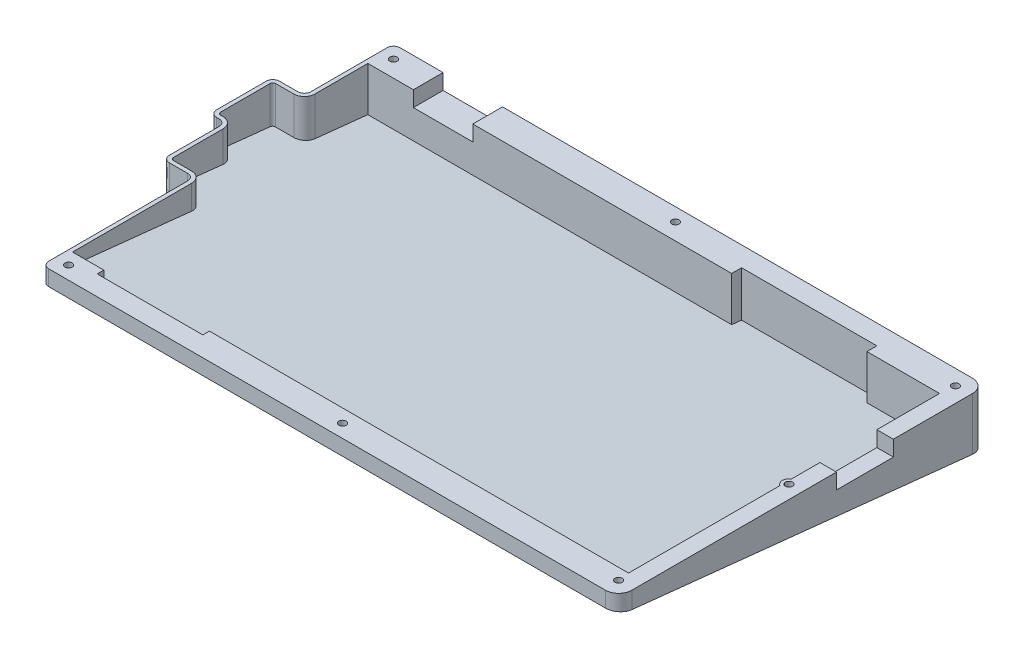
SolidWorks part; units mm, degrees
ref_plane "Front Plane" through (0, 0, 0) normal (0, 0, 1) x (1, 0, 0)
ref_plane "Top Plane" through (0, 0, 0) normal (0, 1, 0) x (1, 0, 0)
ref_plane "Right Plane" through (0, 0, 0) normal (1, 0, 0) x (0, 0, -1)
sketch "Sketch1" plane through (0, 0, 0) normal (0, 1, 0) x (1, 0, 0)
  line L0 (138.4196, 31.7518) -> (125.4196, 31.7518)
  line L1 (-35.0204, 31.7518) -> (107.4196, 31.7518)
  line L2 (140.4196, 29.7518) -> (140.4196, 6.7018)
  line L3 (-34.0204, 3.7518) -> (-34.0204, 22.7518)
  line L4 (136.4596, 27.7518) -> (136.4396, 27.7518)
  line L5 (142.4196, 4.7018) -> (147.9496, 4.7018)
  line L6 (-34.0204, 22.7518) -> (-12.0204, 22.7518)
  line L8 (149.9496, 2.7018) -> (149.9496, -12.3482)
  line L11 (147.9496, -14.3482) -> (147.1896, -14.3482)
  line L14 (145.1896, -16.3482) -> (145.1896, -31.3982)
  line L17 (143.1896, -33.3982) -> (137.6696, -33.3982)
  line L20 (135.6696, -35.3982) -> (135.6696, -77.4982)
  line L21 (-34.0204, -25.6003) -> (-34.0204, -71.4982)
  line L23 (133.6696, -79.4982) -> (-35.0204, -79.4982)
  line L28 (-39.0204, 27.7518) -> (-39.0204, 3.7518)
  line L31 (-34.0204, 3.7518) -> (-39.0204, 3.7518)
  line L32 (-34.0204, -13.4982) -> (-39.0204, -13.4982)
  line L33 (-39.0204, -75.4982) -> (-39.0204, -13.4982)
  line L34 (-34.0204, -71.4982) -> (92.9796, -71.4982)
  line L35 (92.9796, -71.4982) -> (92.9796, -73.4982)
  line L36 (92.9796, -73.4982) -> (124.9796, -73.4982)
  line L37 (124.9796, -73.4982) -> (124.9796, -71.4982)
  line L39 (134.4706, -35.3982) -> (134.4706, -71.4982)
  line L40 (134.4706, -71.4982) -> (124.9796, -71.4982)
  line L41 (137.6696, -32.1992) -> (143.1896, -32.1992)
  line L42 (-34.0204, -13.4982) -> (-34.0204, -22.1362)
  line L43 (143.9906, -31.3982) -> (143.9906, -16.3482)
  line L44 (-12.0204, 22.7518) -> (-12.0204, 25.7518)
  line L45 (147.1896, -13.1492) -> (147.9496, -13.1492)
  line L46 (148.7506, -12.3482) -> (148.7506, 2.7018)
  line L47 (-12.0204, 25.7518) -> (28.9796, 25.7518)
  line L48 (28.9796, 25.7518) -> (28.9796, 22.7518)
  line L49 (28.9796, 22.7518) -> (107.4196, 22.7518)
  line L50 (147.9496, 3.5027) -> (142.4196, 3.5027)
  line L51 (107.4196, 22.7518) -> (107.4196, 31.7518)
  line L52 (139.2206, 6.7018) -> (139.2206, 22.7518)
  line L53 (125.4196, 31.7518) -> (125.4196, 22.7518)
  line L54 (139.2206, 22.7518) -> (125.4196, 22.7518)
  arc A0 (138.4196, 31.7518) -> (140.4196, 29.7518) centre (138.4196, 29.7518) cw
  arc A1 (140.4196, 6.7018) -> (142.4196, 4.7018) centre (142.4196, 6.7018) ccw
  arc A2 (149.9496, 2.7018) -> (147.9496, 4.7018) centre (147.9496, 2.7018) ccw
  arc A3 (149.9496, -12.3482) -> (147.9496, -14.3482) centre (147.9496, -12.3482) cw
  arc A4 (147.1896, -14.3482) -> (145.1896, -16.3482) centre (147.1896, -16.3482) ccw
  arc A5 (145.1896, -31.3982) -> (143.1896, -33.3982) centre (143.1896, -31.3982) cw
  arc A6 (-35.0204, 31.7518) -> (-39.0204, 27.7518) centre (-35.0204, 27.7518) ccw
  arc A7 (-39.0204, -75.4982) -> (-35.0204, -79.4982) centre (-35.0204, -75.4982) ccw
  arc A8 (133.6696, -79.4982) -> (135.6696, -77.4982) centre (133.6696, -77.4982) ccw
  arc A9 (135.6696, -35.3982) -> (137.6696, -33.3982) centre (137.6696, -35.3982) cw
  circle A10 centre (-34.4204, 27.1518) radius 1.1
  circle A11 centre (51.0096, 27.7518) radius 1.1
  circle A12 centre (136.4396, 27.7518) radius 1.1
  circle A13 centre (-34.4204, -74.8982) radius 1.1
  circle A14 centre (48.6296, -75.4982) radius 1.1
  circle A15 centre (131.6496, -75.4982) radius 1.1
  circle A16 centre (-35.0204, -23.8682) radius 1.1
  arc A27 (-34.0204, -22.1362) -> (-34.0204, -25.6003) centre (-35.0204, -23.8682) cw
  arc A28 (139.2206, 6.7018) -> (142.4196, 3.5027) centre (142.4196, 6.7018) ccw
  arc A29 (147.9496, 3.5027) -> (148.7506, 2.7018) centre (147.9496, 2.7018) cw
  arc A30 (148.7506, -12.3482) -> (147.9496, -13.1492) centre (147.9496, -12.3482) cw
  arc A31 (147.1896, -13.1492) -> (143.9906, -16.3482) centre (147.1896, -16.3482) ccw
  arc A32 (143.9906, -31.3982) -> (143.1896, -32.1992) centre (143.1896, -31.3982) cw
  arc A33 (137.6696, -32.1992) -> (134.4706, -35.3982) centre (137.6696, -35.3982) ccw
extrude "Boss-Extrude2" add sketch "Sketch1" against normal blind 4.7 contours L41 A33 L39 L40 L37 L36 L35 L34 L21 A27 L42 L32 L33 A7 L23 A8 L20 A9 L17 A5 L14 A4 L11 A3 L8 A2 L5 A1 L2 A0 L0 L53 L54 L52 A28 L50 A29 L46 A30 L45 A31 L43 A32 A12 A13 A14 A15 | L1 A6 L28 L31 L3 L6 L44 L47 L48 L49 L51 A11 A10 region at (138.2833, 0, -29.6154) region at (31.7683, 0, -26.4895)
move or copy body "Body-Move/Copy1" bodies to move or copy 105 104 copy no rotation origin (55.4646, -2.35, 0) rotation axis (0, 0, 1) rotation angle 180
sketch "Sketch3" plane through (149.9496, 0, 0) normal (1, 0, 0) x (0, 0, -1)
  line L0 (-79.4982, 0) -> (-79.4982, -4.7) construction
  line L1 (-79.4982, 0) -> (-79.4982, -4.7)
  line L2 (31.7518, 0) -> (31.7518, -4.7) construction
  line L3 (31.7518, 0) -> (31.7518, -4.7)
  line L5 (-79.4982, -4.7) -> (31.7518, -16.3928)
  line L6 (31.7518, -16.3928) -> (31.7518, -4.7)
  line L7 (31.7518, -4.7) -> (-79.4982, -4.7)
  line M3 (-75.4982, -4.7) -> (-13.4982, -4.7)
  dimension "D1" = 6
extrude "Boss-Extrude3" add sketch "Sketch3" against normal up to surface (188.97 mm away) contours L6 L7 L5 M3 region at (149.9496, -8.5976, 5.3315) up to face at (-39.0204, -2.35, 4.8232)
sketch "Sketch4" plane through (0, -4.7, 0) normal (0, 1, 0) x (1, 0, 0)
  line L2 (145.9496, -79.4982) -> (149.9496, -79.4982)
  line L3 (149.9496, -79.4982) -> (149.9496, -75.4982)
  line L4 (-29.4904, 6.7018) -> (-29.4904, 29.7518)
  line L5 (-27.4904, 31.7518) -> (-39.0204, 31.7518)
  line L6 (-36.2604, -14.3482) -> (-37.0204, -14.3482)
  line L7 (-39.0204, -12.3482) -> (-39.0204, -79.4982)
  line L8 (-39.0204, -79.4982) -> (-22.7404, -79.4982)
  line L9 (-24.7404, -77.4982) -> (-24.7404, -35.3982)
  line L10 (-26.7404, -33.3982) -> (-32.2604, -33.3982)
  line L11 (-34.2604, -31.3982) -> (-34.2604, -16.3482)
  line L12 (-36.2604, -14.3482) -> (-37.0204, -14.3482)
  line L13 (-39.0204, -12.3482) -> (-39.0204, -79.4982)
  line L14 (-39.0204, -79.4982) -> (-22.7404, -79.4982)
  line L15 (-24.7404, -77.4982) -> (-24.7404, -35.3982)
  line L16 (-26.7404, -33.3982) -> (-32.2604, -33.3982)
  line L17 (-34.2604, -31.3982) -> (-34.2604, -16.3482)
  line L18 (-39.0204, 31.7518) -> (-39.0204, 2.7018)
  line L19 (-37.0204, 4.7018) -> (-31.4904, 4.7018)
  line L20 (-29.4904, 6.7018) -> (-29.4904, 29.7518)
  line L21 (-27.4904, 31.7518) -> (-39.0204, 31.7518)
  line L22 (-39.0204, 31.7518) -> (-39.0204, 2.7018)
  line L23 (-37.0204, 4.7018) -> (-31.4904, 4.7018)
  line L24 (145.9496, -79.4982) -> (149.9496, -79.4982)
  line L25 (149.9496, -79.4982) -> (149.9496, -75.4982)
  line L26 (149.9496, 31.7518) -> (145.9496, 31.7518)
  line L27 (149.9496, 27.7518) -> (149.9496, 31.7518)
  line L28 (149.9496, 31.7518) -> (145.9496, 31.7518)
  line L29 (149.9496, 27.7518) -> (149.9496, 31.7518)
  arc A1 (145.9496, -79.4982) -> (149.9496, -75.4982) centre (145.9496, -75.4982) ccw
  arc A2 (145.9496, -79.4982) -> (149.9496, -75.4982) centre (145.9496, -75.4982) ccw
  arc A3 (-27.4904, 31.7518) -> (-29.4904, 29.7518) centre (-27.4904, 29.7518) ccw
  arc A4 (-37.0204, 4.7018) -> (-39.0204, 2.7018) centre (-37.0204, 2.7018) ccw
  arc A5 (-39.0204, -12.3482) -> (-37.0204, -14.3482) centre (-37.0204, -12.3482) ccw
  arc A6 (-24.7404, -77.4982) -> (-22.7404, -79.4982) centre (-22.7404, -77.4982) ccw
  arc A7 (-24.7404, -35.3982) -> (-26.7404, -33.3982) centre (-26.7404, -35.3982) ccw
  arc A8 (-34.2604, -31.3982) -> (-32.2604, -33.3982) centre (-32.2604, -31.3982) ccw
  arc A9 (-34.2604, -16.3482) -> (-36.2604, -14.3482) centre (-36.2604, -16.3482) ccw
  arc A10 (-39.0204, -12.3482) -> (-37.0204, -14.3482) centre (-37.0204, -12.3482) ccw
  arc A11 (-24.7404, -77.4982) -> (-22.7404, -79.4982) centre (-22.7404, -77.4982) ccw
  arc A12 (-24.7404, -35.3982) -> (-26.7404, -33.3982) centre (-26.7404, -35.3982) ccw
  arc A13 (-34.2604, -31.3982) -> (-32.2604, -33.3982) centre (-32.2604, -31.3982) ccw
  arc A14 (-34.2604, -16.3482) -> (-36.2604, -14.3482) centre (-36.2604, -16.3482) ccw
  arc A15 (-31.4904, 4.7018) -> (-29.4904, 6.7018) centre (-31.4904, 6.7018) ccw
  arc A16 (-27.4904, 31.7518) -> (-29.4904, 29.7518) centre (-27.4904, 29.7518) ccw
  arc A17 (-37.0204, 4.7018) -> (-39.0204, 2.7018) centre (-37.0204, 2.7018) ccw
  arc A18 (-31.4904, 4.7018) -> (-29.4904, 6.7018) centre (-31.4904, 6.7018) ccw
  arc A19 (149.9496, 27.7518) -> (145.9496, 31.7518) centre (145.9496, 27.7518) ccw
  arc A20 (149.9496, 27.7518) -> (145.9496, 31.7518) centre (145.9496, 27.7518) ccw
  dimension "D1" = 0
  dimension "D2" = 0
  dimension "D3" = 0
  dimension "D4" = 0
extrude "Cut-Extrude1" cut sketch "Sketch4" against normal through all
ref_plane "Plane4" through (0, 15, 0) normal (0, 1, 0) x (1, 0, 0)
sketch "Sketch10" plane through (0, 15, 0) normal (0, 1, 0) x (1, 0, 0)
  line L0 (-14.4904, 22.7518) -> (3.5096, 22.7518)
  line L1 (144.9496, 3.7518) -> (144.9496, -13.4982)
  line L27 (-14.4904, 31.7518) -> (-14.4904, 22.7518)
  line L28 (-14.4904, 22.7518) -> (-28.2913, 22.7518)
  line L29 (-28.2913, 22.7518) -> (-28.2913, 6.7018)
  line L30 (-31.4904, 3.5027) -> (-37.0204, 3.5027)
  line L31 (-37.8213, 2.7018) -> (-37.8213, -12.3482)
  line L32 (-37.0204, -13.1492) -> (-36.2604, -13.1492)
  line L33 (-33.0613, -16.3482) -> (-33.0613, -31.3982)
  line L34 (-32.2604, -32.1992) -> (-26.7404, -32.1992)
  line L35 (-23.5413, -35.3982) -> (-23.5413, -71.4982)
  line L36 (-23.5413, -71.4982) -> (-14.0504, -71.4982)
  line L37 (-14.0504, -71.4982) -> (-14.0504, -73.4982)
  line L38 (-14.0504, -73.4982) -> (17.9496, -73.4982)
  line L39 (17.9496, -73.4982) -> (17.9496, -71.4982)
  line L40 (17.9496, -71.4982) -> (144.9496, -71.4982)
  line L41 (144.9496, -71.4982) -> (144.9496, -25.6003)
  line L42 (144.9496, -22.1362) -> (144.9496, -13.4982)
  line L43 (144.9496, -13.4982) -> (149.9496, -13.4982)
  line L44 (149.9496, -13.4982) -> (149.9496, 3.7518)
  line L45 (149.9496, 3.7518) -> (144.9496, 3.7518)
  line L46 (144.9496, 3.7518) -> (144.9496, 22.7518)
  line L47 (144.9496, 22.7518) -> (122.9496, 22.7518)
  line L48 (122.9496, 22.7518) -> (122.9496, 25.7518)
  line L49 (122.9496, 25.7518) -> (81.9496, 25.7518)
  line L50 (81.9496, 25.7518) -> (81.9496, 22.7518)
  line L51 (81.9496, 22.7518) -> (3.5096, 22.7518)
  line L52 (3.5096, 22.7518) -> (3.5096, 31.7518)
  line L53 (3.5096, 31.7518) -> (-14.4904, 31.7518)
  line L54 (-14.4904, 31.7518) -> (-14.4904, 22.7518)
  line L55 (-14.4904, 22.7518) -> (-28.2913, 22.7518)
  line L56 (-28.2913, 22.7518) -> (-28.2913, 6.7018)
  line L57 (-31.4904, 3.5027) -> (-37.0204, 3.5027)
  line L58 (-37.8213, 2.7018) -> (-37.8213, -12.3482)
  line L59 (-37.0204, -13.1492) -> (-36.2604, -13.1492)
  line L60 (-33.0613, -16.3482) -> (-33.0613, -31.3982)
  line L61 (-32.2604, -32.1992) -> (-26.7404, -32.1992)
  line L62 (-23.5413, -35.3982) -> (-23.5413, -71.4982)
  line L63 (-23.5413, -71.4982) -> (-14.0504, -71.4982)
  line L64 (-14.0504, -71.4982) -> (-14.0504, -73.4982)
  line L65 (-14.0504, -73.4982) -> (17.9496, -73.4982)
  line L66 (17.9496, -73.4982) -> (17.9496, -71.4982)
  line L67 (17.9496, -71.4982) -> (144.9496, -71.4982)
  line L68 (144.9496, -71.4982) -> (144.9496, -25.6003)
  line L69 (144.9496, -22.1362) -> (144.9496, -13.4982)
  line L70 (144.9496, -13.4982) -> (149.9496, -13.4982)
  line L71 (149.9496, -13.4982) -> (149.9496, 3.7518)
  line L72 (149.9496, 3.7518) -> (144.9496, 3.7518)
  line L73 (144.9496, 3.7518) -> (144.9496, 22.7518)
  line L74 (144.9496, 22.7518) -> (122.9496, 22.7518)
  line L75 (122.9496, 22.7518) -> (122.9496, 25.7518)
  line L76 (122.9496, 25.7518) -> (81.9496, 25.7518)
  line L77 (81.9496, 25.7518) -> (81.9496, 22.7518)
  line L78 (81.9496, 22.7518) -> (3.5096, 22.7518)
  line L79 (3.5096, 22.7518) -> (3.5096, 31.7518)
  line L80 (3.5096, 31.7518) -> (-14.4904, 31.7518)
  arc A7 (-31.4904, 3.5027) -> (-28.2913, 6.7018) centre (-31.4904, 6.7018) ccw
  arc A8 (-37.0204, 3.5027) -> (-37.8213, 2.7018) centre (-37.0204, 2.7018) ccw
  arc A9 (-37.8213, -12.3482) -> (-37.0204, -13.1492) centre (-37.0204, -12.3482) ccw
  arc A10 (-33.0613, -16.3482) -> (-36.2604, -13.1492) centre (-36.2604, -16.3482) ccw
  arc A11 (-33.0613, -31.3982) -> (-32.2604, -32.1992) centre (-32.2604, -31.3982) ccw
  arc A12 (-23.5413, -35.3982) -> (-26.7404, -32.1992) centre (-26.7404, -35.3982) ccw
  arc A13 (144.9496, -22.1362) -> (144.9496, -25.6003) centre (145.9496, -23.8682) ccw
  arc A14 (-31.4904, 3.5027) -> (-28.2913, 6.7018) centre (-31.4904, 6.7018) ccw
  arc A15 (-37.0204, 3.5027) -> (-37.8213, 2.7018) centre (-37.0204, 2.7018) ccw
  arc A16 (-37.8213, -12.3482) -> (-37.0204, -13.1492) centre (-37.0204, -12.3482) ccw
  arc A17 (-33.0613, -16.3482) -> (-36.2604, -13.1492) centre (-36.2604, -16.3482) ccw
  arc A18 (-33.0613, -31.3982) -> (-32.2604, -32.1992) centre (-32.2604, -31.3982) ccw
  arc A19 (-23.5413, -35.3982) -> (-26.7404, -32.1992) centre (-26.7404, -35.3982) ccw
  arc A20 (144.9496, -22.1362) -> (144.9496, -25.6003) centre (145.9496, -23.8682) ccw
  dimension "D1" = 0
extrude "Cut-Extrude2" cut sketch "Sketch10" against normal through all contours A20 L69 L1 L73 L74 L75 L76 L77 L78 L0 L55 L56 A14 L57 A15 L58 A16 L59 A17 L60 A18 L61 A19 L62 L63 L64 L65 L66 L67 L68 region at (57.9798, 15, 23.6888)
sketch "Sketch11" plane through (144.9496, 0, 0) normal (-1, 0, 0) x (0, 0, 1)
  line L0 (-22.7518, -15.4469) -> (71.4982, -5.5408)
  line L1 (71.4982, -5.5408) -> (71.4982, -3.5408)
  line L2 (71.4982, 0) -> (71.4982, -5.5408) construction
  line L3 (71.4982, -3.5408) -> (-22.7518, -13.4469)
  line L4 (-22.7518, 0) -> (-22.7518, -15.4469) construction
  line L5 (-22.7518, -13.4469) -> (-22.7518, -15.4469)
  dimension "D1" = 2
  dimension "D2" = 2
extrude "Boss-Extrude4" add sketch "Sketch11" along normal up to surface (182.7709 mm away)
sketch "Sketch12" plane through (0, -10.9348, 1.1493) normal (0, 0.9945, -0.1045) x (1, 0, 0)
  line L0 (-29.4904, 7.8943) -> (-29.4904, 24.0327) construction
  line L1 (-29.4904, 24.0327) -> (-37.8213, 24.0327) construction
  line L2 (-37.8213, 24.0327) -> (-37.8213, 5.715) construction
  line L3 (-37.0204, 5.8833) -> (-31.4904, 5.8833) construction
  line L4 (-36.2604, -13.2716) -> (-37.0204, -13.2716) construction
  line L5 (-37.8213, -13.1033) -> (-37.8213, -70.7364) construction
  line L6 (-37.8213, -70.7364) -> (-24.7404, -70.7364) construction
  line L7 (-24.7404, -70.7364) -> (-24.7404, -34.4376) construction
  line L8 (-26.7404, -32.4266) -> (-32.2604, -32.4266) construction
  line L9 (-34.2604, -30.4155) -> (-34.2604, -15.2826) construction
  line L10 (-29.4904, 7.8943) -> (-29.4904, 24.0327)
  line L11 (-29.4904, 24.0327) -> (-37.8213, 24.0327)
  line L12 (-37.8213, 24.0327) -> (-37.8213, 5.715)
  line L13 (-37.0204, 5.8833) -> (-31.4904, 5.8833)
  line L14 (-36.2604, -13.2716) -> (-37.0204, -13.2716)
  line L15 (-37.8213, -13.1033) -> (-37.8213, -70.7364)
  line L16 (-37.8213, -70.7364) -> (-24.7404, -70.7364)
  line L17 (-24.7404, -70.7364) -> (-24.7404, -34.4376)
  line L18 (-26.7404, -32.4266) -> (-32.2604, -32.4266)
  line L19 (-34.2604, -30.4155) -> (-34.2604, -15.2826)
  line L20 (-37.8213, 24.0327) -> (-37.8213, 25.9101)
  line L21 (-29.4904, 24.0327) -> (-29.4904, 27.1127)
  line L22 (-29.4904, 27.1127) -> (-37.8213, 25.9101)
  ellipse E0 centre (-31.4904, 7.8943) end of major axis (-31.4904, 9.9053) minor radius 2 (-31.4904, 5.8833) -> (-29.4904, 7.8943) ccw construction
  ellipse E1 centre (-37.0204, 3.8723) end of major axis (-37.0204, 5.8833) minor radius 2 (-37.0204, 5.8833) -> (-37.8213, 5.715) ccw construction
  ellipse E2 centre (-37.0204, -11.2606) end of major axis (-37.0204, -9.2496) minor radius 2 (-37.8213, -13.1033) -> (-37.0204, -13.2716) ccw construction
  ellipse E3 centre (-26.7404, -34.4376) end of major axis (-26.7404, -32.4266) minor radius 2 (-24.7404, -34.4376) -> (-26.7404, -32.4266) ccw construction
  ellipse E4 centre (-32.2604, -30.4155) end of major axis (-32.2604, -28.4045) minor radius 2 (-34.2604, -30.4155) -> (-32.2604, -32.4266) ccw construction
  ellipse E5 centre (-36.2604, -15.2826) end of major axis (-36.2604, -13.2716) minor radius 2 (-34.2604, -15.2826) -> (-36.2604, -13.2716) ccw construction
  ellipse E6 centre (-31.4904, 7.8943) end of major axis (-31.4904, 9.9053) minor radius 2 (-31.4904, 5.8833) -> (-29.4904, 7.8943) ccw
  ellipse E7 centre (-37.0204, 3.8723) end of major axis (-37.0204, 5.8833) minor radius 2 (-37.0204, 5.8833) -> (-37.8213, 5.715) ccw
  ellipse E8 centre (-37.0204, -11.2606) end of major axis (-37.0204, -9.2496) minor radius 2 (-37.8213, -13.1033) -> (-37.0204, -13.2716) ccw
  ellipse E9 centre (-26.7404, -34.4376) end of major axis (-26.7404, -32.4266) minor radius 2 (-24.7404, -34.4376) -> (-26.7404, -32.4266) ccw
  ellipse E10 centre (-32.2604, -30.4155) end of major axis (-32.2604, -28.4045) minor radius 2 (-34.2604, -30.4155) -> (-32.2604, -32.4266) ccw
  ellipse E11 centre (-36.2604, -15.2826) end of major axis (-36.2604, -13.2716) minor radius 2 (-34.2604, -15.2826) -> (-36.2604, -13.2716) ccw
  ellipse M1 centre (-31.4904, 7.8943) end of major axis (-31.4904, 9.9053) minor radius 2 (-31.4904, 5.8833) -> (-29.4904, 7.8943) ccw
  line M2 (-29.4904, 7.8943) -> (-29.4904, 24.0327)
  line M3 (-29.4904, 24.0327) -> (-37.8213, 24.0327)
  line M4 (-37.8213, 24.0327) -> (-37.8213, 5.715)
  ellipse M5 centre (-37.0204, 3.8723) end of major axis (-37.0204, 5.8833) minor radius 2 (-37.8213, 5.715) -> (-37.0204, 5.8833) cw
  line M6 (-37.0204, 5.8833) -> (-31.4904, 5.8833)
extrude "Cut-Extrude6" cut sketch "Sketch12" against normal blind 15 contours L19 E11 L14 E8 L15 L16 L17 E9 L18 E10 | L21 L22 L20 M3 | M6 M1 M2 M3 M4 M5 region at (-33.6783, -12.5032, -13.7734) region at (-33.319, -13.579, -24.0085) region at (-31.8603, -5.8979, 49.0727)
sketch "Sketch20" plane through (0, 0, -22.7518) normal (0, 0, -1) x (-1, 0, 0)
  line L4 (-81.9496, -15.4469) -> (-81.9496, -13.4469)
  line L5 (-81.9496, -13.4469) -> (-122.9496, -13.4469)
  line L6 (-122.9496, -13.4469) -> (-122.9496, -15.4469)
  line L7 (-122.9496, -15.4469) -> (-81.9496, -15.4469)
  line L8 (-81.9496, -15.4469) -> (-81.9496, -13.4469)
  line L9 (-81.9496, -13.4469) -> (-122.9496, -13.4469)
  line L10 (-122.9496, -13.4469) -> (-122.9496, -15.4469)
  line L11 (-122.9496, -15.4469) -> (-81.9496, -15.4469)
  dimension "D1" = 0
sketch "Sketch21" plane through (122.9496, 0, 0) normal (-1, 0, 0) x (0, 0, 1)
  line L0 (-22.7518, -15.4469) -> (-22.7518, -13.4469)
  line L1 (-22.7518, -15.4469) -> (-25.7518, -15.7622)
  line L2 (-25.7518, -15.7622) -> (-25.7518, -13.7622)
  line L4 (-22.7518, -13.4469) -> (-25.7518, -13.7622)
  dimension "D1" = 2
extrude "Boss-Extrude6" add sketch "Sketch21" along normal up to surface (41 mm away)
sketch "Sketch22" plane through (17.9496, 0, 0) normal (-1, 0, 0) x (0, 0, 1)
  line L0 (71.4982, -5.5408) -> (73.4982, -5.3306)
  line L1 (71.4982, -5.5408) -> (71.4982, -3.5408)
  line L2 (71.4982, -3.5408) -> (73.4982, -3.3306)
  line L3 (73.4982, 0) -> (73.4982, -5.3306) construction
  line L4 (73.4982, -3.3306) -> (73.4982, -5.3306)
  dimension "D1" = 2
extrude "Boss-Extrude7" add sketch "Sketch22" along normal up to surface (32 mm away)
